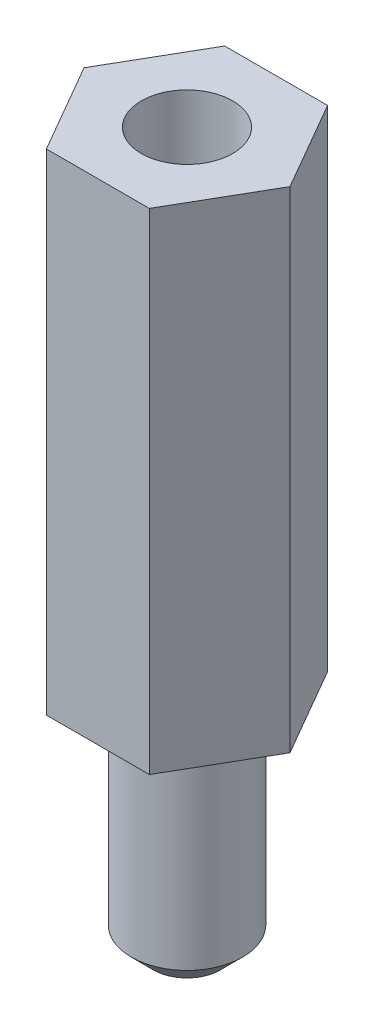
SolidWorks part; units mm, degrees
ref_plane "Front Plane" through (0, 0, 0) normal (0, 0, 1) x (1, 0, 0)
ref_plane "Top Plane" through (0, 0, 0) normal (0, 1, 0) x (1, 0, 0)
ref_plane "Right Plane" through (0, 0, 0) normal (1, 0, 0) x (0, 0, -1)
sketch "Sketch1" plane through (0, 0, 0) normal (0, 1, 0) x (1, 0, 0)
  line L1 (1.1547, -2) -> (2.3094, 0)
  line L2 (2.3094, 0) -> (1.1547, 2)
  line L3 (1.1547, 2) -> (-1.1547, 2)
  line L4 (-1.1547, 2) -> (-2.3094, 0)
  line L5 (-2.3094, 0) -> (-1.1547, -2)
  line L6 (-1.1547, -2) -> (1.1547, -2)
  circle A0 centre (0, 0) radius 2 construction
  circle A1 centre (0, 0) radius 1.25
  dimension "D2" = 2.5
  dimension "D1" = 4
extrude "Boss-Extrude1" add sketch "Sketch1" along normal blind 11 contours L5 L6 L1 L2 L3 L4 A1 | A1 region at (0, 0, 1.9389) region at (0, 0, 0)
extrude "Boss-Extrude2" add sketch "Sketch1<3>" against normal blind 5 contours A1
sketch "Sketch1<3>" plane through (0, 0, 0) normal (0, 1, 0) x (1, 0, 0) same geometry as "Sketch1"
chamfer "Chamfer1" distance 0.5 angle 45 1 edges at (0, -5, 1.25)
hole_wizard "M2.5 Tapped Hole1" positions "Sketch2" profile "Sketch4" tap size "M2.5" standard "ISO"
sketch "Sketch2" plane through (0, 11, 0) normal (0, 1, 0) x (1, 0, 0)
  point P0 (0, 0)
sketch "Sketch4" plane through (0, 11, 0) normal (1, 0, 0) x (0, 0, 1)
  line L0 (0, 0) -> (0, 10.6159)
  line L1 (0, 10.6159) -> (1.025, 10)
  line L2 (1.025, 10) -> (1.025, 0)
  line L5 (1.025, 0) -> (0, 0)
  line L10 (0, 10.6159) -> (-1.025, 10) construction
  line L11 (0, -6.35) -> (0, 107.95) construction
  dimension "Tap Drill Dia." = 2.05
  dimension "Tap Drill Depth" = 10
  dimension "Drill Angle" = 118
cosmetic thread "Hole Thread1" parameters "D1"=5, "D2"=2.5
other "Freeze***"
